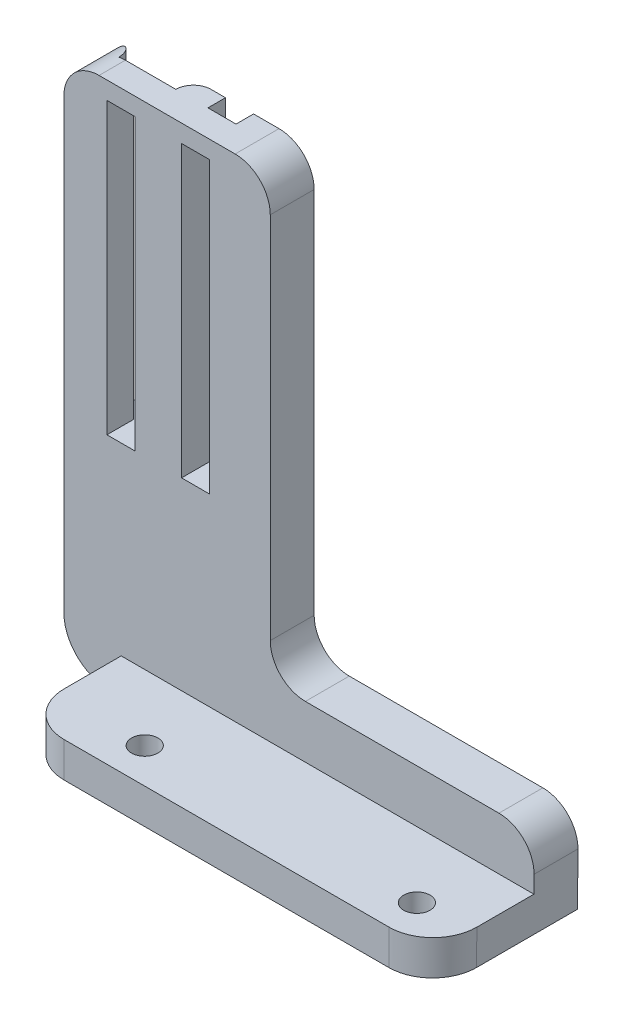
SolidWorks part; units mm, degrees
material "ABS generico"
ref_plane "Front Plane" through (0, 0, 0) normal (0, 0, 1) x (1, 0, 0)
ref_plane "Top Plane" through (0, 0, 0) normal (0, 1, 0) x (1, 0, 0)
ref_plane "Right Plane" through (0, 0, 0) normal (1, 0, 0) x (0, 0, -1)
sketch "Sketch1" plane through (0, 0, 0) normal (0, 0, 1) x (1, 0, 0)
  line L0 (24.5834, -25) -> (24.6606, -15)
  line L1 (24.5834, -25) -> (-28.9167, -25)
  line L2 (-5.4167, 0) -> (-5.4167, 35) construction
  line L3 (-5.4167, 35) -> (-12.3167, 35)
  line L5 (22.0833, -25) -> (-28.9167, 32.7358) construction
  line L6 (24.6606, -15) -> (-5.4167, -15)
  line L7 (-13.9167, 0) -> (-13.9167, 35) construction
  line L8 (-28.9167, -25) -> (-28.9167, 35)
  line L9 (24.5834, -15) -> (-30.9167, -15) construction
  line L10 (-12.3167, 0) -> (-12.3167, 35)
  line L11 (-15.5167, 0) -> (-15.5167, 35)
  line L12 (-5.4167, -15) -> (-5.4167, 35)
  line L13 (-24.0167, 35) -> (-28.9167, 35)
  line L14 (-15.5167, 35) -> (-20.8167, 35)
  line L15 (24.5834, -25) -> (-30.9167, -25) construction
  line L16 (-24.0167, 0) -> (-24.0167, 35)
  line L18 (-18, -10) -> (-18, 25) construction
  line L20 (-20.8167, 0) -> (-20.8167, 35)
  line L22 (-20.8167, 0) -> (-24.0167, 0)
  line L24 (-12.3167, 0) -> (-15.5167, 0)
  line L25 (-15.5167, -15) -> (-15.5167, 35) construction
  line L26 (-13.9167, -15) -> (-13.9167, 35) construction
  line L27 (-12.3167, -15) -> (-12.3167, 35) construction
  point P0 (0, 0)
  point P1 (-30.9167, 35)
  point P3 (26.5, 35)
  point P6 (-18, -25)
  point P10 (-16.4, -25)
  point P12 (-19.6, -25)
  point P18 (22.2762, 0)
  point P19 (-26.5, -10)
  dimension "D3" = 10
  dimension "D7" = 1.6
  dimension "D8" = 1.6
  dimension "D9" = 8.5
extrude "Extrude1" add sketch "Sketch1" along normal blind 5
sketch "Sketch3" plane through (0, 0, 5) normal (0, 0, 1) x (1, 0, 0)
  line L0 (22.0833, -10.5045) -> (22.0833, -32.7354) construction
  line L2 (-15.5167, 0) -> (-15.5167, -46) construction
  line L3 (-15.5167, -23) -> (22.0833, -23) construction
  line L4 (3.2833, -23) -> (3.2833, 0) construction
  line L5 (-15.5167, -25) -> (35.4785, -25) construction
  line L6 (-22.3949, -21) -> (24.6143, -21)
  line L8 (-22.3949, -25) -> (24.5834, -25)
  line L9 (-22.3949, -25) -> (-22.3949, -21)
  line L10 (-15.5167, -21) -> (22.0833, -25) construction
  line L11 (-15.5167, -25) -> (22.0833, -21) construction
  line L12 (24.6143, -21) -> (24.5834, -25)
  line L13 (24.5834, -25) -> (24.6606, -15) construction
  line L14 (-28.9167, -25) -> (24.5834, -25) construction
  dimension "D1" = 2
extrude "Extrude2" add sketch "Sketch3" along normal blind 11.5
sketch "Sketch4" plane through (0, 35, 0) normal (0, 1, 0) x (1, 0, 0)
  line L0 (-20.8167, 0) -> (-24.0167, 0) construction
  line L1 (-25.6667, -2) -> (-19.1667, -2)
  line L2 (-25.6667, -2) -> (-25.6667, 2)
  line L3 (-25.6667, 2) -> (-19.1667, 2)
  line L4 (-19.1667, -2) -> (-19.1667, 2)
  line L5 (-25.6667, -2) -> (-19.1667, 2) construction
  line L6 (-25.6667, 2) -> (-19.1667, -2) construction
  point P0 (-22.4167, 0)
  dimension "D1" = 6.5
  dimension "D2" = 4
sketch "Sketch5" plane through (0, -21, 0) normal (0, 1, 0) x (1, 0, 0)
  line L0 (17.6784, -12.4986) -> (-11.1079, -12.5014) construction
  line L1 (3.2852, -12.5) -> (3.2852, -16.5) construction
  line L2 (-15.5167, -16.5) -> (22.0833, -16.5) construction
  circle A0 centre (-12.2148, -12.5015) radius 1.5
  circle A1 centre (18.7852, -12.5015) radius 1.5
  dimension "D1" = 3
  dimension "D2" = 15.5
  dimension "D3" = 4
extrude "Extrude3" cut sketch "Sketch5" against normal up to surface (4 mm away) up to face at (-9.4529, -25, 8.125)
fillet "Fillet2" radius 5 2 edges at (-22.3949, -23, 16.5) (24.5988, -23, 16.5)
fillet "Fillet3" radius 4 4 edges at (24.6606, -15, 2.5) (-5.4167, -15, 2.5) (-5.4167, 35, 2.5) (-28.9167, 35, 2.5)
fillet "Fillet4" radius 5 1 edges at (-28.9167, -25, 2.5)
extrude "Extrude4" cut sketch "Sketch4" against normal up to surface (35 mm away) up to face at (-22.4167, 0, 2.5)
fillet "Fillet1" radius 2 2 edges at (-19.1667, 17.5, 0) (-25.6667, 17.4645, 0)
sketch "Sketch6" plane through (0, 0, 5) normal (0, 0, 1) x (1, 0, 0)
  line L0 (-24.0167, 35) -> (-12.3167, 35)
  line L1 (-12.3167, 35) -> (-12.3167, 32.9851)
  line L2 (-12.3167, 35) -> (-12.3167, 0) construction
  line L3 (-12.3167, 32.9851) -> (-24.0167, 32.9851)
  line L4 (-24.0167, 0) -> (-24.0167, 35) construction
  line L5 (-24.0167, 32.9851) -> (-24.0167, 35)
extrude "Extrude5" add sketch "Sketch6" against normal up to surface (3 mm away) up to face at (-24.857, 20.9894, 2)
